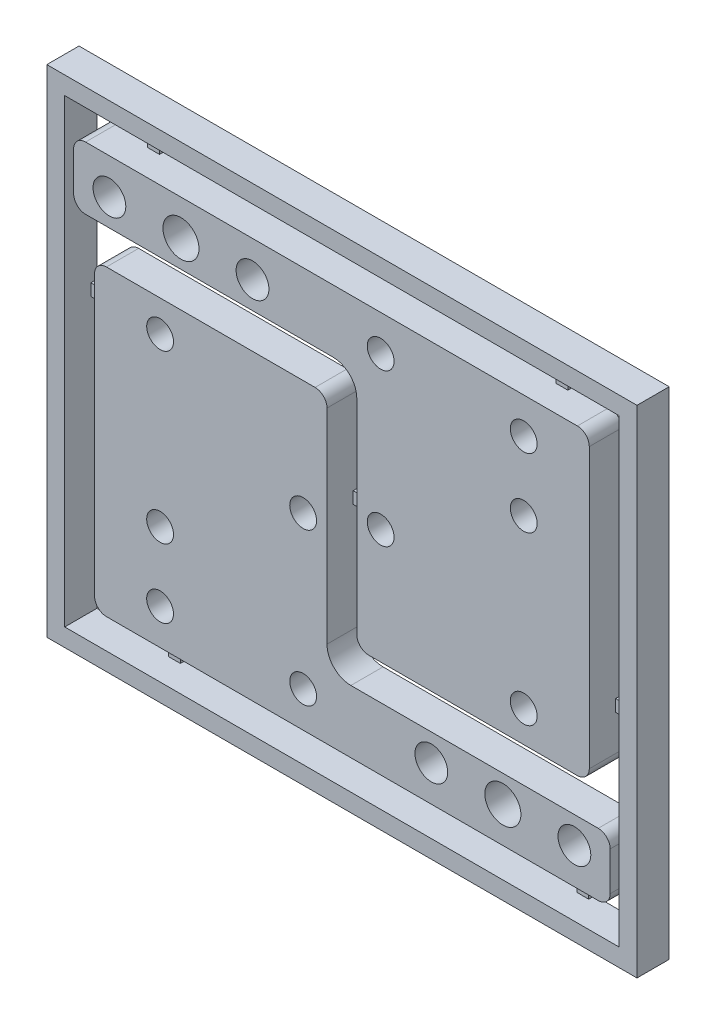
SolidWorks part; units mm, degrees
ref_plane "Front Plane" through (0, 0, 0) normal (0, 0, 1) x (1, 0, 0)
ref_plane "Top Plane" through (0, 0, 0) normal (0, 1, 0) x (1, 0, 0)
ref_plane "Right Plane" through (0, 0, 0) normal (1, 0, 0) x (0, 0, -1)
sketch "Sketch1" plane through (0, 0, 0) normal (0, 0, 1) x (1, 0, 0)
  line L0 (11, 45.55) -> (11, 17.55) construction
  line L1 (0, 0) -> (86.5, 0)
  line L2 (0, 0) -> (0, 50.8)
  line L3 (0, 50.8) -> (39, 50.8)
  line L4 (86.5, 0) -> (86.5, 10.5)
  line L5 (11, 31.55) -> (35, 31.55) construction
  line L6 (39, 50.8) -> (39, 10.5)
  line L7 (39, 10.5) -> (86.5, 10.5)
  circle A0 centre (56.5, 6) radius 2.75
  circle A1 centre (11, 17.55) radius 2.25
  circle A2 centre (80.5, 6) radius 2.75
  circle A5 centre (11, 45.55) radius 2.25
  circle A6 centre (-21, 45.55) radius 2.25 [skipped]
  circle A7 centre (-21, 17.55) radius 2.25 [skipped]
  circle A8 centre (35, 31.55) radius 2.25
  dimension "D1" = 11.55
  dimension "D3" = 24
  dimension "D5" = 5.5
  dimension "D12" = 4.5
  dimension "D2" = 45.5
  dimension "D4" = 6
  dimension "D8" = 50.8
  dimension "D9" = 6
  dimension "D10" = 11
  dimension "D11" = 28
  dimension "D13" = 24
  dimension "D14" = 4.5
  dimension "D15" = 39
  dimension "D6" = 2
  dimension "D7" = 2
extrude "Boss-Extrude1" add sketch "Sketch1" along normal blind 5.4
fillet "Fillet1" radius 4 1 edges at (39, 10.5, 2.7)
sketch "Sketch2" plane through (0, 0, 5.4) normal (0, 0, 1) x (1, 0, 0)
  line L0 (56.5, 6) -> (80.5, 6) construction
  circle A0 centre (68.5, 6) radius 3.025
  dimension "D1" = 6.05
extrude "Cut-Extrude1" cut sketch "Sketch2" against normal through all
sketch "Sketch3" plane through (0, 0, 5.4) normal (0, 0, 1) x (1, 0, 0)
  line L0 (0, 6) -> (38.0502, 6) construction
  line L1 (0, 50.8) -> (0, 0) construction
  line L2 (0, 0) -> (86.5, 0) construction
  line L3 (23, 0) -> (23, 58.1921) construction
  circle A0 centre (11, 6) radius 2.25
  circle A1 centre (35, 6) radius 2.25
  dimension "D1" = 6
  dimension "D2" = 4.5
  dimension "D3" = 23
  dimension "D4" = 24
extrude "Cut-Extrude2" cut sketch "Sketch3" against normal blind 5
sketch "Sketch4" plane through (0, 0, 5.4) normal (0, 0, 1) x (1, 0, 0)
  line L0 (41.5, 0) -> (41.5, 33.6) construction
  line L1 (0, 0) -> (86.5, 0) construction
  line L2 (41.5, 33.6) -> (12.4673, 33.6) construction
  line L3 (39, 14.5) -> (39, 50.8) construction
  line L5 (39, 50.8) -> (0, 50.8) construction
  point P9 (0, 0)
  dimension "D1" = 2.5
  dimension "D2" = 17.2
ref_axis "Axis1" through (41.5, 33.6, 5.4) along (0, 0, 1)
pattern_circular "CirPattern1" count 2 over 360 about axis through (41.5, 33.6, 5.4) along (0, 0, 1) of bodies 103
sketch "Sketch5" plane through (0, 0, 0) normal (0, 0, -1) x (-1, 0, 0)
  line L0 (0, 50.8) -> (0, 0) construction
  line L1 (-88, 72.2) -> (5, 72.2)
  line L2 (-88, 72.2) -> (-88, -5)
  line L3 (-88, -5) -> (5, -5)
  line L4 (5, 72.2) -> (5, -5)
  line L5 (0, 0) -> (-86.5, 0) construction
  line L6 (-83, 16.4) -> (-83, 67.2) construction
  line L7 (-83, 67.2) -> (3.5, 67.2) construction
  line L8 (-91, 75.2) -> (-91, -8)
  line L9 (-91, -8) -> (8, -8)
  line L10 (8, 75.2) -> (8, -8)
  line L11 (-91, 75.2) -> (8, 75.2)
  dimension "D1" = 5
  dimension "D2" = 5
  dimension "D3" = 5
  dimension "D4" = 5
  dimension "D5" = 3
fillet "Fillet2" radius 2 5 edges at (83, 67.2, 2.7) (-3.5, 67.2, 2.7) (-3.5, 56.7, 2.7) (83, 16.4, 2.7) (44, 16.4, 2.7)
fillet "Fillet3" radius 2 5 edges at (86.5, 10.5, 2.7) (86.5, 0, 2.7) (0, 0, 2.7) (0, 50.8, 2.7) (39, 50.8, 2.7)
extrude "Boss-Extrude3" add sketch "Sketch5" against normal up to surface (5.4 mm away) separate body up to face at (69.75, 61.2, 5.4)
sketch "Sketch6" plane through (0, 0, 0) normal (0, 0, -1) x (-1, 0, 0)
  line L0 (-44, 52.7) -> (-44, 18.4) construction
  line L1 (-44, 34.6) -> (-39, 34.6)
  line L2 (-44, 34.6) -> (-44, 32.6)
  line L3 (-44, 32.6) -> (-39, 32.6)
  line L4 (-39, 34.6) -> (-39, 32.6)
  line L5 (-39, 14.5) -> (-39, 48.8) construction
  line L6 (-41.5, 33.6) -> (-12.4673, 33.6) construction
  line L7 (0, 48.8) -> (0, 2) construction
  line L8 (0, 42.8) -> (5, 42.8)
  line L9 (0, 42.8) -> (0, 40.8)
  line L10 (0, 40.8) -> (5, 40.8)
  line L11 (5, 42.8) -> (5, 40.8)
  line L12 (5, -5) -> (5, 72.2) construction
  line L13 (-2, 0) -> (-84.5, 0) construction
  line L14 (-10, 0) -> (-8, 0)
  line L15 (-10, 0) -> (-10, -5)
  line L16 (-10, -5) -> (-8, -5)
  line L17 (-8, 0) -> (-8, -5)
  line L18 (-88, -5) -> (5, -5) construction
  line L19 (-83, 18.4) -> (-83, 65.2) construction
  line L20 (-78.5, 0) -> (-76.5, 0)
  line L21 (-78.5, 0) -> (-78.5, -5)
  line L22 (-78.5, -5) -> (-76.5, -5)
  line L23 (-76.5, 0) -> (-76.5, -5)
  line L24 (-83, 24.4) -> (-88, 24.4)
  line L25 (-83, 24.4) -> (-83, 26.4)
  line L26 (-83, 26.4) -> (-88, 26.4)
  line L27 (-88, 24.4) -> (-88, 26.4)
  line L28 (-88, 72.2) -> (-88, -5) construction
  line L29 (-81, 67.2) -> (1.5, 67.2) construction
  line L30 (-75, 67.2) -> (-73, 67.2)
  line L31 (-75, 67.2) -> (-75, 72.2)
  line L32 (-75, 72.2) -> (-73, 72.2)
  line L33 (-73, 67.2) -> (-73, 72.2)
  line L34 (5, 72.2) -> (-88, 72.2) construction
  line L35 (3.5, 65.2) -> (3.5, 58.7) construction
  line L36 (-6.5, 67.2) -> (-4.5, 67.2)
  line L37 (-6.5, 67.2) -> (-6.5, 72.2)
  line L38 (-6.5, 72.2) -> (-4.5, 72.2)
  line L39 (-4.5, 67.2) -> (-4.5, 72.2)
  line L40 (-37, 50.8) -> (-2, 50.8) construction
  line L41 (-86.5, 2) -> (-86.5, 8.5) construction
  line L42 (-46, 16.4) -> (-81, 16.4) construction
  dimension "D1" = 1
  dimension "D2" = 1
  dimension "D3" = 8
  dimension "D4" = 8
  dimension "D5" = 8
  dimension "D6" = 8
  dimension "D7" = 8
  dimension "D8" = 8
extrude "Boss-Extrude4" add sketch "Sketch6" against normal blind 1
